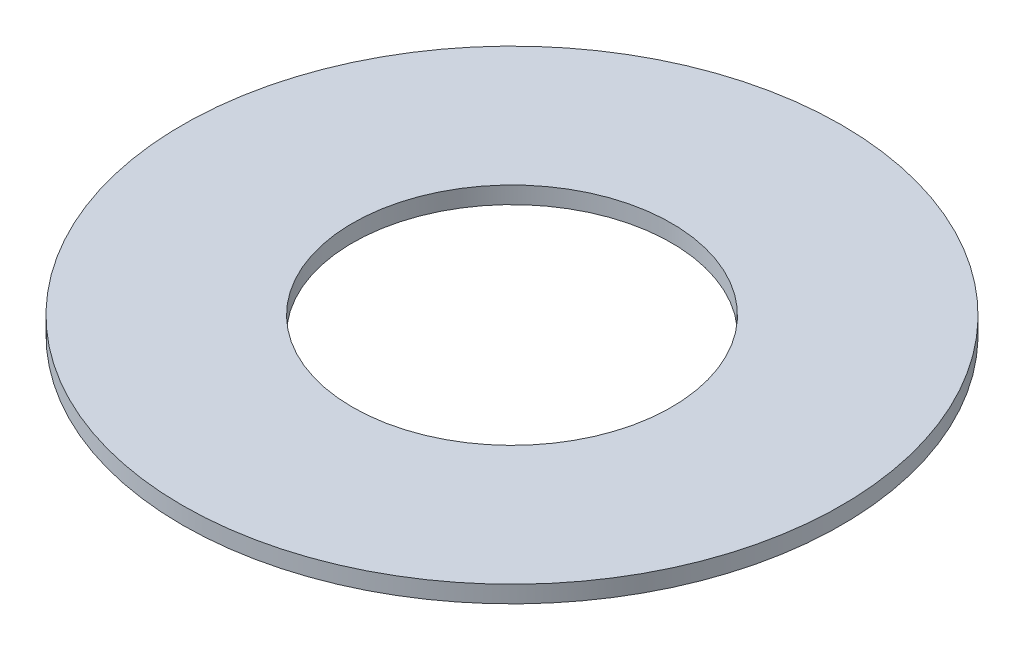
SolidWorks part; units mm, degrees
ref_plane "Front Plane" through (0, 0, 0) normal (0, 0, 1) x (1, 0, 0)
ref_plane "Top Plane" through (0, 0, 0) normal (0, 1, 0) x (1, 0, 0)
ref_plane "Right Plane" through (0, 0, 0) normal (1, 0, 0) x (0, 0, -1)
sketch "Sketch1" plane through (0, 0, 0) normal (0, 1, 0) x (1, 0, 0)
  circle A0 centre (0, 0) radius 77.5
  dimension "FLANGE_OD" = 155
extrude "Boss-Extrude1" add sketch "Sketch1" along normal blind 4
sketch "Sketch2" plane through (0, 0, 0) normal (0, 1, 0) x (1, 0, 0)
  circle A0 centre (0, 0) radius 37.5
  dimension "BORE_D" = 75
extrude "Cut-Extrude1" cut sketch "Sketch2" along normal through all
sketch "Sketch3" plane through (0, 4, 0) normal (0, 1, 0) x (1, 0, 0)
  circle A0 centre (0, 0) radius 20.7686 construction
  circle A1 centre (-20.7686, 0) radius 2.8159
  dimension "BOLT_D" = 5.6319
  dimension "BOLT_PCD" = 41.5373
extrude "Cut-Extrude2" cut sketch "Sketch3" against normal blind 2.538 rebuild error yes
pattern_circular "CirPattern1" count 3 over 360 rebuild error yes
